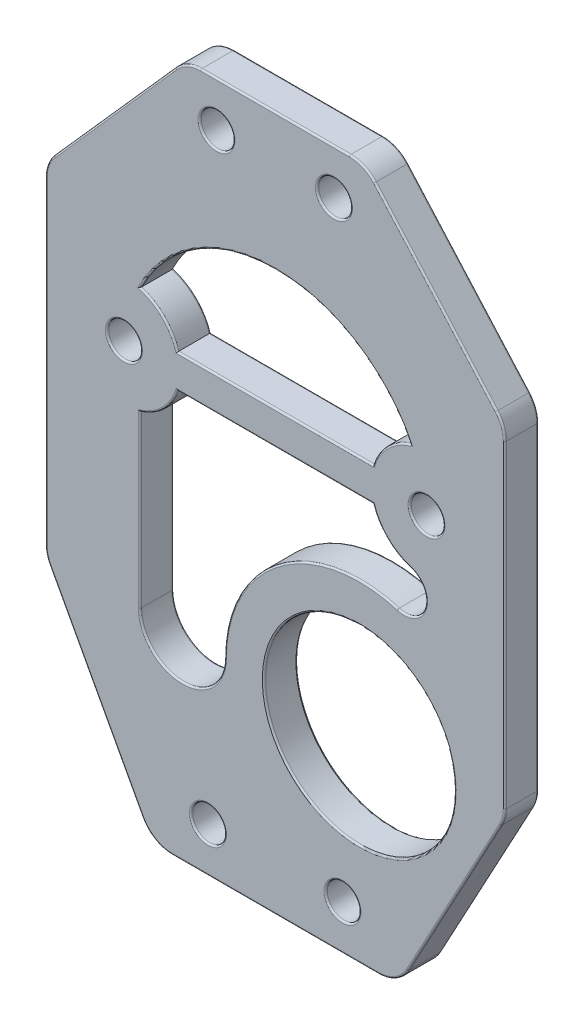
SolidWorks part; units mm, degrees
ref_plane "Front Plane" through (0, 0, 0) normal (0, 0, 1) x (1, 0, 0)
ref_plane "Top Plane" through (0, 0, 0) normal (0, 1, 0) x (1, 0, 0)
ref_plane "Right Plane" through (0, 0, 0) normal (1, 0, 0) x (0, 0, -1)
sketch "Sketch1" plane through (0, 0, 0) normal (0, 0, 1) x (1, 0, 0)
  line L0 (0, 0) -> (0, 62) construction
  line L1 (11, 0) -> (-11, 0)
  line L2 (-11, 0) -> (-20.5, 17.5997)
  line L3 (-20.5, 17.5997) -> (-20.5, 47.8997)
  line L4 (7.9898, 62) -> (-7.9898, 62)
  line L5 (-7.9898, 62) -> (-20.5, 47.8997)
  line L6 (11, 0) -> (20.5, 17.5997)
  line L7 (20.5, 17.5997) -> (20.5, 47.8997)
  line L8 (7.9898, 62) -> (20.5, 47.8997)
  line L9 (7.5, 17.5997) -> (20.5, 17.5997) construction
  line L10 (-8.7303, 39.0997) -> (8.7303, 39.0997)
  line L11 (8.7303, 36.0997) -> (-8.7303, 36.0997) construction
  line L13 (8.7303, 39.0997) -> (-8.7303, 39.0997) construction
  line L15 (13.5, 37.5997) -> (10.9482, 29.0936) construction
  line L16 (-12.0633, 32.8106) -> (-12.0633, 17.5997)
  line L17 (8.7303, 36.0997) -> (-8.7303, 36.0997)
  circle A0 centre (-5.2398, 58) radius 1.5
  circle A1 centre (-13.5, 37.5997) radius 1.5
  circle A2 centre (-6, 4) radius 1.5
  circle A3 centre (6, 4) radius 1.5
  circle A4 centre (13.5, 37.5997) radius 1.5
  circle A5 centre (5.2398, 58) radius 1.5
  circle A6 centre (7.5, 17.5997) radius 8.5
  circle A7 centre (13.5, 37.5997) radius 5 construction
  arc A8 (-8.7303, 39.0997) -> (-8.7303, 36.0997) centre (-13.5, 37.5997) ccw construction
  circle A9 centre (7.5, 17.5997) radius 12 construction
  arc A10 (-12.0633, 42.3888) -> (12.0633, 42.3888) centre (0, 36.3285) cw
  arc A11 (-12.0633, 42.3888) -> (-8.7303, 39.0997) centre (-13.5, 37.5997) cw
  arc A12 (12.0633, 42.3888) -> (8.7303, 39.0997) centre (13.5, 37.5997) ccw
  arc A13 (12.0633, 32.8106) -> (10.9482, 29.0936) centre (11.5057, 30.9521) cw
  arc A14 (10.9482, 29.0936) -> (-4.5, 17.5997) centre (7.5, 17.5997) ccw
  arc A15 (-8.7303, 36.0997) -> (-12.0633, 32.8106) centre (-13.5, 37.5997) cw
  arc A16 (8.7303, 36.0997) -> (12.0633, 32.8106) centre (13.5, 37.5997) ccw
  circle A17 centre (-13.5, 37.5997) radius 5 construction
  arc A18 (-12.0633, 17.5997) -> (-4.5, 17.5997) centre (-8.2816, 17.5997) ccw
  dimension "D9" = 3
  dimension "D14" = 17
  dimension "D18" = 13.5
  dimension "D1" = 62
  dimension "D2" = 6
  dimension "D3" = 4
  dimension "D4" = 11
  dimension "D5" = 20
  dimension "D6" = 30.3
  dimension "D7" = 10.3
  dimension "D8" = 7
  dimension "D10" = 18.85
  dimension "D11" = 2.75
  dimension "D12" = 4
  dimension "D13" = 20.5
  dimension "D19" = 3
  dimension "D20" = 13
  dimension "D15" = 3.5
  dimension "D16" = 3.5
  dimension "D17" = 3.5
extrude "Boss-Extrude1" add sketch "Sketch1" along normal blind 3
fillet "Fillet1" radius 3 8 edges at (-11, 0, 1.5) (-20.5, 17.5997, 1.5) (-20.5, 47.8997, 1.5) (-7.9898, 62, 1.5) (7.9898, 62, 1.5) (20.5, 47.8997, 1.5) (20.5, 17.5997, 1.5) (11, 0, 1.5)
fillet "Fillet2" radius 0.15 68 edges at (13.3642, 30.3946, 0) (0.3368, 27.2272, 0) (-8.2816, 13.8181, 0) (-12.0633, 25.2052, 0) (-9.9879, 34.0409, 0) (0, 36.0997, 0) (9.9879, 34.0409, 0) (10.7472, 0.4237, 0) (15.9951, 9.2539, 0) (20.4086, 17.6228, 0) (20.5, 32.5592, 0) (20.3047, 47.8256, 0) (14.3146, 54.8714, 0) (7.8712, 61.7361, 0) (0, 62, 0) (-7.8712, 61.7361, 0) (-14.3146, 54.8714, 0) (-20.3047, 47.8256, 0) (-20.5, 32.5592, 0) (-20.4086, 17.6228, 0) (-15.9951, 9.2539, 0) (-10.7472, 0.4237, 0) (0, 0, 0) (0, 49.8285, 0) (9.9879, 41.1586, 0) (0, 39.0997, 0) (-9.9879, 41.1586, 0) (-3.7398, 58, 0) (-12, 37.5997, 0) (-4.5, 4, 0) (4.5, 4, 0) (12, 37.5997, 0) (3.7398, 58, 0) (16, 17.5997, 0) (-9.9879, 34.0409, 3) (-12.0633, 25.2052, 3) (-8.2816, 13.8181, 3) (0.3368, 27.2272, 3) (13.3642, 30.3946, 3) (9.9879, 34.0409, 3) (0, 36.0997, 3) (16, 17.5997, 3) (12, 37.5997, 3) (-4.5, 4, 3) (-3.7398, 58, 3) (-20.4086, 17.6228, 3) (-20.5, 32.5592, 3) (-20.3047, 47.8256, 3) (-14.3146, 54.8714, 3) (-7.8712, 61.7361, 3) (0, 62, 3) (7.8712, 61.7361, 3) (14.3146, 54.8714, 3) (20.3047, 47.8256, 3) (20.5, 32.5592, 3) (20.4086, 17.6228, 3) (15.9951, 9.2539, 3) (10.7472, 0.4237, 3) (0, 0, 3) (-10.7472, 0.4237, 3) (-15.9951, 9.2539, 3) (9.9879, 41.1586, 3) (0, 49.8285, 3) (-9.9879, 41.1586, 3) (0, 39.0997, 3) (-12, 37.5997, 3) (4.5, 4, 3) (3.7398, 58, 3)
